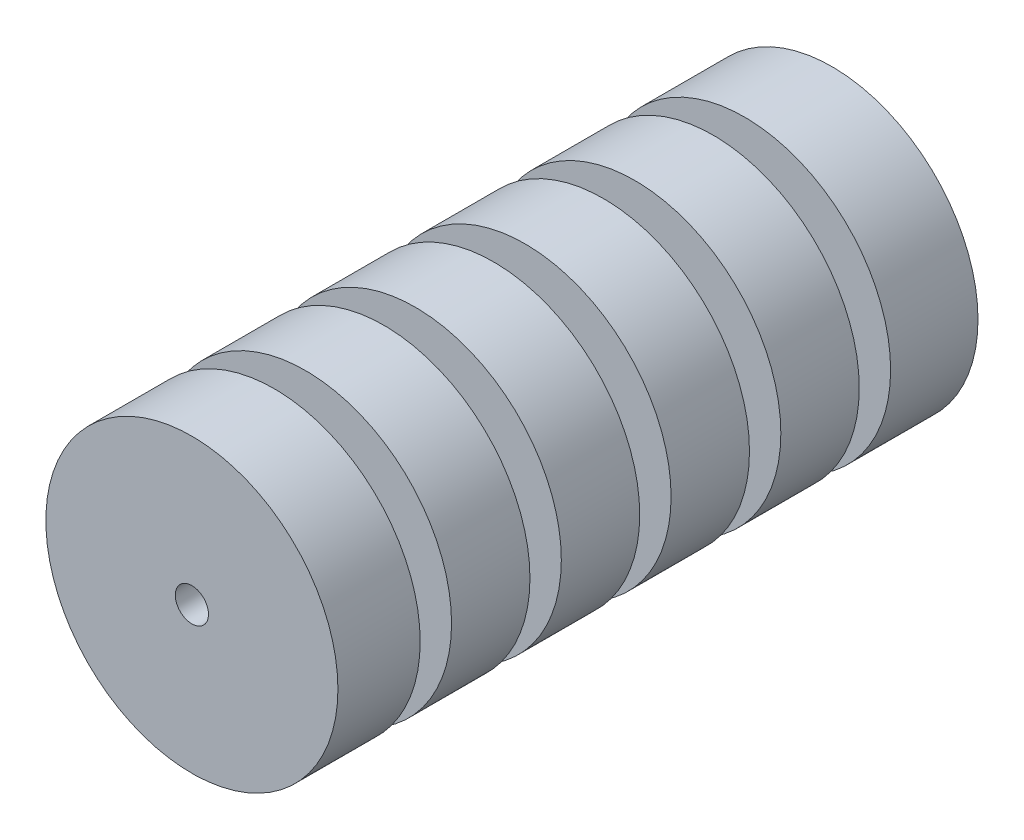
SolidWorks part; units mm, degrees
material "RUBBER 65A Test Modulus"
ref_plane "Front Plane" through (0, 0, 0) normal (0, 0, 1) x (1, 0, 0)
ref_plane "Top Plane" through (0, 0, 0) normal (0, 1, 0) x (1, 0, 0)
ref_plane "Right Plane" through (0, 0, 0) normal (1, 0, 0) x (0, 0, -1)
sketch "Sketch3" plane through (0, 0, 0) normal (0, 0, 1) x (1, 0, 0)
  circle A0 centre (0, 0) radius 27.94
  dimension "D1" = 55.88
extrude "Boss-Extrude2" add sketch "Sketch3" along normal blind 122.46
ref_axis "Axis2" through (0, 0, 121.5887) along (0, 0, -1)
sketch "Sketch5" plane through (0, 0, 122.46) normal (0, 0, 1) x (1, 0, 0)
  circle A0 centre (0, 0) radius 3.175
  dimension "D1" = 6.35
extrude "Cut-Extrude1" cut sketch "Sketch5" against normal through all contours A0
sketch "Sketch4" plane through (0, 0, 0) normal (0, 1, 0) x (1, 0, 0)
  line L0 (0, -122.46) -> (0, 0) construction
  line L1 (-27.94, -122.46) -> (27.94, -122.46) construction
  line L3 (-27.94, -106.72) -> (-13.94, -106.72)
  line L4 (-27.94, -106.72) -> (-27.94, -100.72)
  line L5 (-27.94, -100.72) -> (-13.94, -100.72)
  line L6 (-13.94, -106.72) -> (-13.94, -100.72)
  line L63 (-27.94, -85.72) -> (-27.94, -79.72)
  line L64 (-27.94, -85.72) -> (-13.94, -85.72)
  line L65 (-13.94, -85.72) -> (-13.94, -79.72)
  line L66 (-27.94, -79.72) -> (-13.94, -79.72)
  line L67 (-27.94, -64.72) -> (-27.94, -58.72)
  line L68 (-27.94, -64.72) -> (-13.94, -64.72)
  line L69 (-13.94, -64.72) -> (-13.94, -58.72)
  line L70 (-27.94, -58.72) -> (-13.94, -58.72)
  line L71 (-27.94, -43.72) -> (-27.94, -37.72)
  line L72 (-27.94, -43.72) -> (-13.94, -43.72)
  line L73 (-13.94, -43.72) -> (-13.94, -37.72)
  line L74 (-27.94, -37.72) -> (-13.94, -37.72)
  line L75 (-27.94, -22.72) -> (-27.94, -16.72)
  line L76 (-27.94, -22.72) -> (-13.94, -22.72)
  line L77 (-13.94, -22.72) -> (-13.94, -16.72)
  line L78 (-27.94, -16.72) -> (-13.94, -16.72)
  line L91 (-27.94, -106.72) -> (-27.94, -85.72) construction
  line L92 (-27.94, -1.72) -> (-27.94, 4.28) [skipped]
  line L93 (-27.94, -1.72) -> (-13.94, -1.72) [skipped]
  line L94 (-13.94, -1.72) -> (-13.94, 4.28) [skipped]
  line L95 (-27.94, 4.28) -> (-13.94, 4.28) [skipped]
  line L96 (-27.94, 19.28) -> (-27.94, 25.28) [skipped]
  line L97 (-27.94, 19.28) -> (-13.94, 19.28) [skipped]
  line L98 (-13.94, 19.28) -> (-13.94, 25.28) [skipped]
  line L99 (-27.94, 25.28) -> (-13.94, 25.28) [skipped]
  line L100 (-27.94, 40.28) -> (-27.94, 46.28) [skipped]
  line L101 (-27.94, 40.28) -> (-13.94, 40.28) [skipped]
  line L102 (-13.94, 40.28) -> (-13.94, 46.28) [skipped]
  line L103 (-27.94, 46.28) -> (-13.94, 46.28) [skipped]
  dimension "D1" = 15.74
  dimension "D2" = 6
  dimension "D3" = 27.94
  dimension "D4" = 14
  dimension "D6" = 21
  dimension "D5" = 8
revolve "Cut-Revolve1" cut sketch "Sketch4" angle 360 about L0
shell "Shell1" thickness 3
sketch "Sketch10" plane through (0, 0, 0) normal (0, 0, -1) x (-1, 0, 0)
  line L0 (0, 27.94) -> (0, -27.94) construction
  line L1 (-27.94, 0) -> (27.94, 0) construction
  line L2 (-1, 27.9221) -> (-1, 3.0134)
  line L3 (1, 3.0134) -> (1, 27.9221)
  line L4 (3.0134, 1) -> (27.9221, 1)
  line L5 (3.0134, -1) -> (27.9221, -1)
  line L6 (-1, -3.0134) -> (-1, -27.9221)
  line L7 (1, -3.0134) -> (1, -27.9221)
  line L8 (-27.9221, -1) -> (-3.0134, -1)
  line L9 (-27.9221, 1) -> (-3.0134, 1)
  circle A0 centre (0, 0) radius 27.94 construction
  circle A1 centre (0, 0) radius 3.175 construction
  arc A2 (-1, -27.9221) -> (1, -27.9221) centre (0, 0) ccw
  arc A3 (27.9221, -1) -> (27.9221, 1) centre (0, 0) ccw
  arc A4 (1, 27.9221) -> (-1, 27.9221) centre (0, 0) ccw
  arc A5 (-27.9221, 1) -> (-27.9221, -1) centre (0, 0) ccw
  arc A6 (-1, -3.0134) -> (1, -3.0134) centre (0, 0) ccw
  arc A7 (-3.0134, 1) -> (-3.0134, -1) centre (0, 0) ccw
  arc A8 (1, 3.0134) -> (-1, 3.0134) centre (0, 0) ccw
  arc A9 (3.0134, -1) -> (3.0134, 1) centre (0, 0) ccw
  dimension "D1" = 1
  dimension "D2" = 1
  dimension "D3" = 1
  dimension "D4" = 1
  dimension "D5" = 1
extrude "Boss-Extrude3" add sketch "Sketch10" against normal up to surface (122.46 mm away) up to face at (3.175, 0, 122.46)
ref_plane "Plane1" through (0, 0, 0) normal (-0.7071, -0.7071, 0) x (0, 0, -1)
ref_plane "Plane2" through (0, 0, 0) normal (-0.7071, 0.7071, 0) x (0, 0, -1)
ref_plane "Plane3" through (0, 0, 0) normal (0, 1, 0) x (1, 0, 0)
sketch "Sketch13" plane through (0, 0, 0) normal (0, 1, 0) x (1, 0, 0)
  line L0 (-30.3872, -37.72) -> (-13.9041, -37.72)
  line L1 (-30.3872, -16.72) -> (-13.9041, -16.72)
  line L2 (-30.3872, -16.72) -> (-30.3872, -22.72)
  line L3 (-30.3872, -22.72) -> (-13.9041, -22.72)
  line L4 (-13.9041, -16.72) -> (-13.9041, -22.72)
  line L5 (-30.3872, -37.72) -> (-30.3872, -43.72)
  line L6 (-30.3872, -43.72) -> (-13.9041, -43.72)
  line L7 (-13.9041, -37.72) -> (-13.9041, -43.72)
  line L8 (-30.3872, -58.72) -> (-13.9041, -58.72)
  line L9 (-30.3872, -58.72) -> (-30.3872, -64.72)
  line L10 (-30.3872, -64.72) -> (-13.9041, -64.72)
  line L11 (-13.9041, -58.72) -> (-13.9041, -64.72)
  line L12 (-30.3872, -79.72) -> (-13.9041, -79.72)
  line L13 (-30.3872, -79.72) -> (-30.3872, -85.72)
  line L14 (-30.3872, -85.72) -> (-13.9041, -85.72)
  line L15 (-13.9041, -79.72) -> (-13.9041, -85.72)
  line L16 (-30.3872, -100.72) -> (-13.9041, -100.72)
  line L17 (-30.3872, -100.72) -> (-30.3872, -106.72)
  line L18 (-30.3872, -106.72) -> (-13.9041, -106.72)
  line L19 (-13.9041, -100.72) -> (-13.9041, -106.72)
  dimension "D2" = 6
  dimension "D1" = 5
revolve "Cut-Revolve2" cut sketch "Sketch13" angle 360 about axis through (0, 0, 121.5887) along (0, 0, -1)
sketch "Sketch15" plane through (0, 0, 0) normal (0, 0, -1) x (-1, 0, 0)
  line L0 (0, 0) -> (0, 28.5004) construction
  line L1 (0, 0) -> (-22.0052, 22.0052) construction
equation "\"inwall\"= .75"
equation "\"outwall\"=2"
